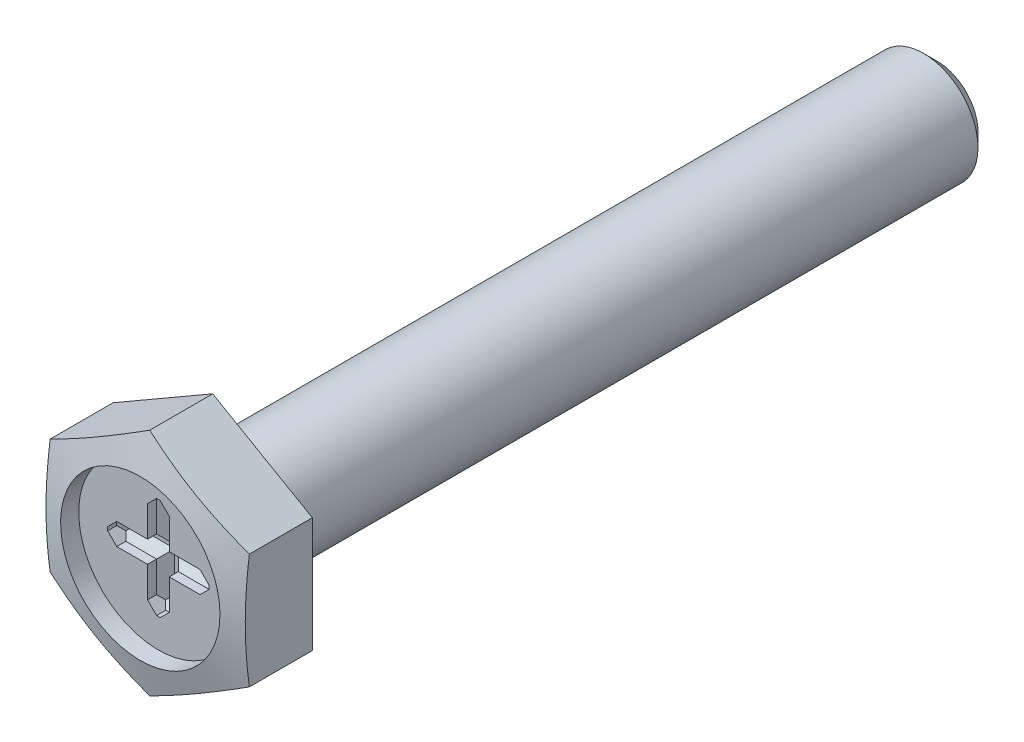
SolidWorks part; units mm, degrees
ref_plane "前视基准面" through (0, 0, 0) normal (0, 0, 1) x (1, 0, 0)
ref_plane "上视基准面" through (0, 0, 0) normal (0, 1, 0) x (1, 0, 0)
ref_plane "右视基准面" through (0, 0, 0) normal (1, 0, 0) x (0, 0, -1)
sketch "草图1" plane through (0, 0, 0) normal (0, 0, 1) x (1, 0, 0)
  line L1 (0, 3.1754) -> (-2.75, 1.5877)
  line L2 (-2.75, 1.5877) -> (-2.75, -1.5877)
  line L3 (-2.75, -1.5877) -> (0, -3.1754)
  line L4 (0, -3.1754) -> (2.75, -1.5877)
  line L5 (2.75, -1.5877) -> (2.75, 1.5877)
  line L6 (2.75, 1.5877) -> (0, 3.1754)
  circle A0 centre (0, 0) radius 2.75 construction
  dimension "s" = 5.5
extrude "凸台-拉伸1" add sketch "草图1" along normal blind 2
ref_axis "基准轴1" through (0, 0, 0) along (0, 0, -1)
sketch "草图3" plane through (0, 0, 0) normal (0, 0, 1) x (1, 0, 0)
  circle A0 centre (0, 0) radius 1.5
  dimension "d" = 3
extrude "凸台-拉伸3" add sketch "草图3" against normal blind 20
cosmetic thread "装饰螺纹线1" parameters "D2"=2.459
sketch "草图4" plane through (0, 0, 0) normal (1, 0, 0) x (0, 0, -1)
  line L0 (2.242, 0) -> (-1.4572, 0) construction
  line L2 (-2, 11) -> (-2, 2.2)
  line L3 (-2, 11) -> (0.358, 11)
  line L6 (-2, 1.5877) -> (-2, 3.1754) construction
  line L7 (-2, 2.2) -> (0.358, 11)
  dimension "D3" = 11
  dimension "D2" = 2.2
  dimension "D1" = 15
revolve "切除-旋转1" cut sketch "草图4" angle 360 about L0
sketch "草图7" plane through (0, 0, 2) normal (0, 0, 1) x (1, 0, 0)
  circle A0 centre (0, 0) radius 2.2
  circle A6 centre (0, 0) radius 2.2 construction
extrude "切除-拉伸3" cut sketch "草图7" against normal blind 0.5
sketch "草图6" plane through (0, 0, 1.5) normal (0, 0, 1) x (1, 0, 0)
  line L1 (1.4, 0.3) -> (-1.4, 0.3)
  line L2 (1.4, 0.3) -> (1.4, -0.3)
  line L3 (1.4, -0.3) -> (-1.4, -0.3)
  line L4 (-1.4, 0.3) -> (-1.4, -0.3)
  line L5 (0, -0.3) -> (0, 0.3) construction
  line L6 (1.4, 0) -> (-1.4, 0) construction
  line L7 (0.3, 1.4) -> (-0.3, 1.4)
  line L8 (0.3, 1.4) -> (0.3, -1.4)
  line L9 (0.3, -1.4) -> (-0.3, -1.4)
  line L10 (-0.3, 1.4) -> (-0.3, -1.4)
  line L11 (0, -1.4) -> (0, 1.4) construction
  line L12 (0.3, 0) -> (-0.3, 0) construction
  circle A2 centre (0, 0) radius 2.2 construction
  point P0 (0, 0)
  point P4 (0, 0)
  dimension "D1" = 0.6
  dimension "D2" = 0.8
extrude "切除-拉伸1" cut sketch "草图6" against normal offset from surface (0.5 mm away) 1 contours L10 L9 L8 L7 | L3 L4 L1 L2 up to face at (1.5, 0, 0)
chamfer "倒角1" distance 0.375 angle 45 1 edges at (1.5, 0, -20)
fillet "圆角1" radius 0.1 1 edges at (1.5, 0, 0)
ref_plane "基准面1" through (0, 0, 0) normal (0, 0, -1) x (-1, 0, 0)
chamfer "倒角2" distance 0.25 angle 45 12 edges at (0.85, 0.3, 1) (1.4, 0, 1) (0.85, -0.3, 1) (0.3, -0.85, 1) (0, -1.4, 1) (-0.3, -0.85, 1) (-0.85, -0.3, 1) (-1.4, 0, 1) (-0.85, 0.3, 1) (-0.3, 0.85, 1) (0, 1.4, 1) (0.3, 0.85, 1)
chamfer "倒角3" distance 0.25 angle 45 8 edges at (-1.4, 0.3, 1.375) (-1.4, -0.3, 1.375) (0.3, -1.4, 1.375) (-0.3, -1.4, 1.375) (1.4, -0.3, 1.375) (1.4, 0.3, 1.375) (0.3, 1.4, 1.375) (-0.3, 1.4, 1.375)
equation "\"D2@草图4\"=\"s@草图1\" * 0.4"
equation "\"D3@草图4\"=\"s@草图1\" * 2"
equation "\"D1@倒角1\"=\"d@草图3\" / 8"
